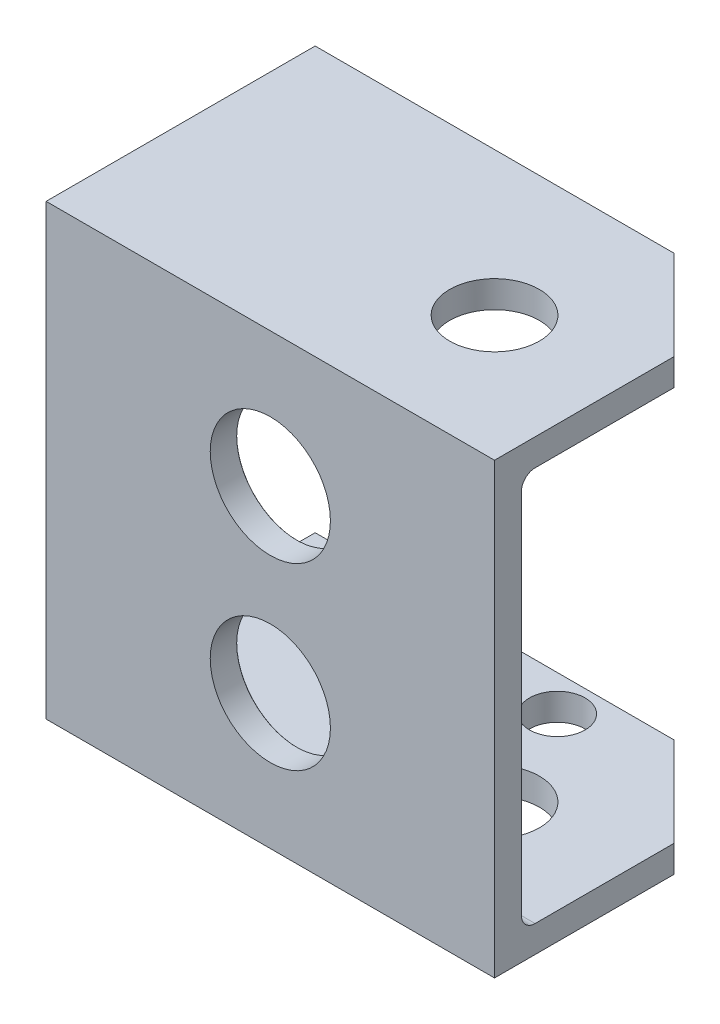
SolidWorks part; units mm, degrees
ref_plane "Front Plane" through (0, 0, 0) normal (0, 0, 1) x (1, 0, 0)
ref_plane "Top Plane" through (0, 0, 0) normal (0, 1, 0) x (1, 0, 0)
ref_plane "Right Plane" through (0, 0, 0) normal (1, 0, 0) x (0, 0, -1)
sketch "Sketch1" plane through (0, 0, 0) normal (0, 0, 1) x (1, 0, 0)
  line L1 (-12.5, 12.5) -> (12.5, 12.5)
  line L2 (-12.5, 12.5) -> (-12.5, -12.5)
  line L3 (-12.5, -12.5) -> (12.5, -12.5)
  line L4 (12.5, 12.5) -> (12.5, -12.5)
  line L5 (-12.5, 12.5) -> (12.5, -12.5) construction
  line L6 (-12.5, -12.5) -> (12.5, 12.5) construction
  point P0 (0, 0)
  dimension "D1" = 25
  dimension "D2" = 25
extrude "Boss-Extrude1" add sketch "Sketch1" along normal blind 1.5
sketch "Sketch2" plane through (0, 0, 0) normal (0, 0, -1) x (-1, 0, 0)
  line L0 (-12.5, -12.5) -> (-12.5, 12.5) construction
  line L1 (12.5, 12.5) -> (-12.5, 12.5)
  line L2 (12.5, 12.5) -> (12.5, 11)
  line L3 (12.5, 11) -> (-12.5, 11)
  line L4 (-12.5, 12.5) -> (-12.5, 11)
  line L5 (12.5, 0) -> (-12.5, 0) construction
  line L6 (12.5, 12.5) -> (12.5, -12.5) construction
  line L7 (12.5, -11) -> (-12.5, -11)
  line L8 (-12.5, -12.5) -> (-12.5, -11)
  line L9 (12.5, -12.5) -> (-12.5, -12.5)
  line L10 (12.5, -12.5) -> (12.5, -11)
  dimension "D1" = 1.5
extrude "Boss-Extrude2" add sketch "Sketch2" along normal blind 13.5
sketch "Sketch10" plane through (0, -12.5, 0) normal (0, -1, 0) x (1, 0, 0)
  line L0 (12.5, 1.5) -> (12.5, -13.5) construction
  line L2 (-12.5, 1.5) -> (12.5, 1.5) construction
  line L3 (12.5, -13.5) -> (-12.5, -13.5) construction
  line L4 (12.5, 1.5) -> (12.5, -13.5) construction
  circle A0 centre (5.5, -5.5) radius 2.5
  circle A1 centre (3, -11.5) radius 1.55
  point P8 (5.4742, 1.5)
  point P9 (0, 0)
  dimension "D1" = 3.1
  dimension "D2" = 5
  dimension "D3" = 7
  dimension "D4" = 7
  dimension "D5" = 2
  dimension "D6" = 9.5
extrude "Cut-Extrude1" cut sketch "Sketch10" against normal through all contours A0 region at (5.5, -12.5, -5.5)
extrude "Cut-Extrude2" cut sketch "Sketch10<3>" against normal up to surface (1.5 mm away) contours A1 region at (3, -12.5, -11.5) up to face at (8, -11, -5.5)
sketch "Sketch10<3>" plane through (0, -12.5, 0) normal (0, -1, 0) x (1, 0, 0) same geometry as "Sketch10"
fillet "Fillet1" radius 0.762 2 edges at (0, -11, 0) (0, 11, 0)
chamfer "Chamfer1" distance 5 angle 45 2 edges at (12.5, -11.75, -13.5) (12.5, 11.75, -13.5)
sketch "Sketch12" plane through (0, 0, 0) normal (0, 0, -1) x (-1, 0, 0)
  line L0 (-13.6435, 0) -> (16.7073, 0) construction
hole_wizard "CBORE for M3 SBHCS1" positions "Sketch13" profile "Sketch14" counterbore size "M3" standard "ANSI Metric" end condition through all
sketch "Sketch13" plane through (0, 0, 0) normal (0, 0, -1) x (-1, 0, 0)
  line L0 (-13.6435, 0) -> (16.7073, 0) construction
  line L1 (-12.5, -10.238) -> (-12.5, 10.238) construction
  line L2 (-13.3169, 0) -> (20.491, 0) construction
  point P0 (0, 5)
  point P14 (0, -5)
  dimension "D1" = 5
  dimension "D2" = 12.5
sketch "Sketch14" plane through (0, 5, 0) normal (1, 0, 0) x (0, 1, 0)
  line L0 (0, 0) -> (0, 1.5)
  line L1 (0, 1.5) -> (1.7, 1.5)
  line L3 (1.7, 1.5) -> (1.7, 1.65)
  line L4 (3.35, 1.65) -> (1.7, 1.65)
  line L5 (3.35, 1.65) -> (3.35, 0.025)
  line L6 (3.35, 0.025) -> (3.375, 0)
  line L7 (3.375, 0) -> (0, 0)
  line L8 (-3.35, 0.025) -> (-3.375, 0) construction
  line L11 (0, -6.35) -> (0, 107.95) construction
  dimension "Thru Hole Dia." = 3.4
  dimension "Thru Hole Depth" = 1.5
  dimension "C'Bore Dia." = 6.7
  dimension "C'Bore Depth" = 1.65
  dimension "Near C'Sink Dia." = 6.75
  dimension "Near C'Sink Angle" = 90
